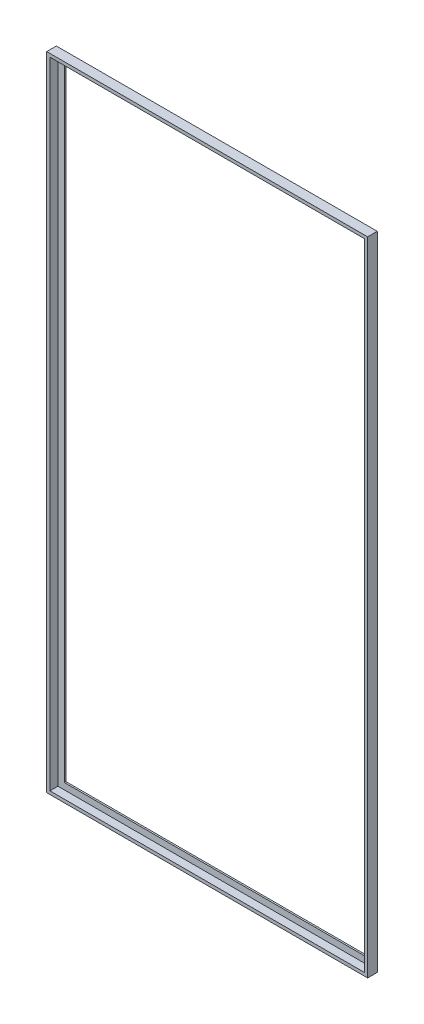
SolidWorks part; units mm, degrees
ref_plane "Alzado" through (0, 0, 0) normal (0, 0, 1) x (1, 0, 0)
ref_plane "Planta" through (0, 0, 0) normal (0, 1, 0) x (1, 0, 0)
ref_plane "Vista lateral" through (0, 0, 0) normal (1, 0, 0) x (0, 0, -1)
sketch "Croquis1" plane through (0, 0, 0) normal (0, 0, 1) x (1, 0, 0)
  line L0 (10, 10) -> (10, 1990)
  line L1 (0, 0) -> (1000, 0)
  line L2 (0, 0) -> (0, 2000)
  line L3 (0, 2000) -> (1000, 2000)
  line L4 (1000, 0) -> (1000, 2000)
  line L5 (10, 1990) -> (990, 1990)
  line L6 (990, 10) -> (990, 1990)
  line L7 (10, 10) -> (990, 10)
  line L8 (30, 1970) -> (970, 1970)
  line L9 (970, 30) -> (970, 1970)
  line L10 (30, 30) -> (970, 30)
  line L11 (30, 30) -> (30, 1970)
  dimension "D1" = 10
  dimension "D2" = 30
extrude "Saliente-Extruir1" add sketch "Croquis1" along normal blind 5 contours L0 L7 L6 L5 L10 L11 L8 L9 region at (12.2093, 1000, 0)
extrude "Saliente-Extruir2" add sketch "Croquis1<4>" along normal blind 30 contours L1 L4 L3 L2 L7 L0 L5 L6 region at (2.2361, 1000, 0)
sketch "Croquis1<4>" plane through (0, 0, 0) normal (0, 0, 1) x (1, 0, 0) same geometry as "Croquis1"
